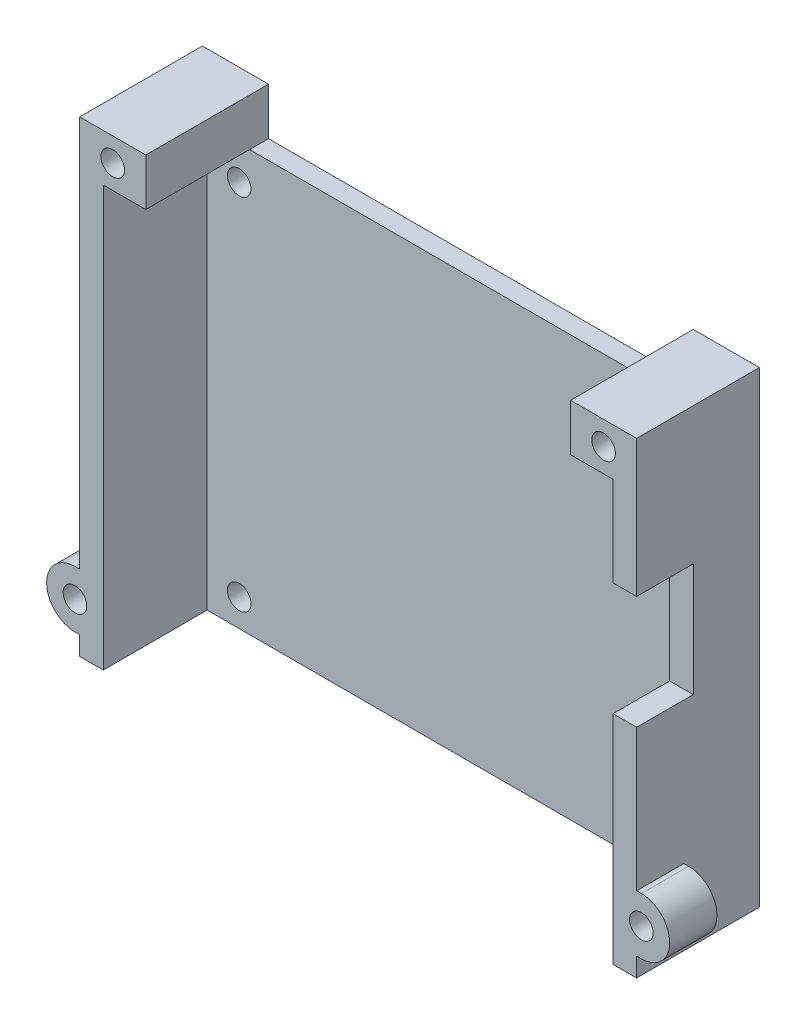
SolidWorks part; units mm, degrees
ref_plane "Front Plane" through (0, 0, 0) normal (0, 0, 1) x (1, 0, 0)
ref_plane "Top Plane" through (0, 0, 0) normal (0, 1, 0) x (1, 0, 0)
ref_plane "Right Plane" through (0, 0, 0) normal (1, 0, 0) x (0, 0, -1)
sketch "Sketch1" plane through (0, 0, 0) normal (0, 1, 0) x (1, 0, 0)
  line L0 (0, 0) -> (2.5, 0)
  line L1 (0, 0) -> (59, 0) construction
  line L2 (0, 0) -> (0, 13)
  line L3 (0, 13) -> (59, 13)
  line L4 (59, 0) -> (59, 13)
  line L5 (2.5, 0) -> (2.5, 11)
  line L6 (2.5, 11) -> (56.5, 11)
  line L7 (56.5, 11) -> (56.5, 0)
  line L8 (56.5, 0) -> (59, 0)
  dimension "D1" = 59
  dimension "D2" = 13
  dimension "D3" = 2.5
  dimension "D4" = 11
  dimension "D5" = 54
extrude "Boss-Extrude1" add sketch "Sketch1" along normal blind 44.5
sketch "Sketch2" plane through (59, 0, 0) normal (1, 0, 0) x (0, 0, -1)
  line L0 (0, 0) -> (0, 23) construction
  line L1 (0, 44.5) -> (0, 0) construction
  line L2 (0, 23) -> (6, 23)
  line L3 (6, 23) -> (6, 35)
  line L4 (6, 35) -> (0, 35)
  line L5 (0, 35) -> (0, 23)
  dimension "D1" = 23
  dimension "D2" = 6
  dimension "D3" = 12
extrude "Cut-Extrude1" cut sketch "Sketch2" against normal blind 10
sketch "Sketch3" plane through (0, 0, -13) normal (0, 0, -1) x (-1, 0, 0)
  line L0 (-59, 0) -> (-59, 8) construction
  line L1 (-59, 44.5) -> (-59, 0) construction
  line L2 (-59, 8) -> (-59, 2)
  line L3 (-59, 5) -> (-59.5, 5) construction
  line L4 (-59, 8) -> (-59.5, 8)
  line L5 (-59, 2) -> (-59.5, 2)
  line L6 (0, 0) -> (0, 8) construction
  line L7 (0, 44.5) -> (0, 0) construction
  line L8 (0, 8) -> (0.5, 8)
  line L9 (0, 8) -> (0, 2)
  line L10 (0, 2) -> (0.5, 2)
  line L11 (0, 5) -> (0.5, 5) construction
  arc A0 (-59.5, 8) -> (-59.5, 2) centre (-59.5, 5) ccw
  circle A1 centre (-59.5, 5) radius 1.25
  arc A2 (0.5, 8) -> (0.5, 2) centre (0.5, 5) cw
  circle A3 centre (0.5, 5) radius 1.25
  line M5 (0, 0) -> (0, 44.5)
  line M7 (-59, 44.5) -> (-59, 0)
  dimension "D4" = 3
  dimension "D5" = 2.5
  dimension "D11" = 3
  dimension "D12" = 2.5
  dimension "D1" = 8
  dimension "D2" = 6
  dimension "D3" = 0.5
  dimension "D6" = 8
  dimension "D7" = 0.5
  dimension "D8" = 6
  dimension "D9" = 0.5
extrude "Boss-Extrude2" add sketch "Sketch3" against normal blind 13 contours A1 L4 A0 L5 M7 | A3 L10 A2 L8 M5 region at (59.0695, 7.0728, -13) region at (-0.25, 7.9305, -13)
extrude "Cut-Extrude2" cut sketch "Sketch3<3>" against normal blind 13 contours L2 A1 | L9 A3 region at (58.6906, 5, -13) region at (0.3094, 5, -13)
sketch "Sketch3<3>" plane through (0, 0, -13) normal (0, 0, -1) x (-1, 0, 0) same geometry as "Sketch3"
sketch "Sketch4" plane through (0, 44.5, 0) normal (0, 1, 0) x (1, 0, 0)
  line L0 (59, 13) -> (0, 13) construction
  line L1 (0, 0) -> (7, 0)
  line L2 (0, 0) -> (0, 13)
  line L3 (0, 13) -> (7, 13)
  line L4 (7, 0) -> (7, 13)
  line L6 (59, 0) -> (52, 0)
  line L7 (59, 0) -> (59, 13)
  line L8 (59, 13) -> (52, 13)
  line L9 (52, 0) -> (52, 13)
  dimension "D1" = 7
  dimension "D2" = 7
extrude "Boss-Extrude3" add sketch "Sketch4" along normal blind 5
sketch "Sketch5" plane through (0, 0, -13) normal (0, 0, -1) x (-1, 0, 0)
  line L0 (-59, 49.5) -> (-52, 44.5) construction
  line L1 (0, 49.5) -> (-7, 44.5) construction
  line L2 (-53, 73.35) -> (-6, 73.35) construction
  line L3 (-6, 73.35) -> (-6, 47) construction
  line L4 (-6, 47) -> (-3.5, 47) construction
  line L5 (-52, 49.5) -> (-52, 44.5) construction
  line L6 (-29.5, 73.35) -> (-29.5, -5.4278) construction
  circle A0 centre (-55.5, 47) radius 1.25
  circle A1 centre (-3.5, 47) radius 1.25
  circle A2 centre (-6, 73.35) radius 1.25
  circle A3 centre (-53, 73.35) radius 1.25
  dimension "D1" = 2.5
  dimension "D3" = 2.5
  dimension "D4" = 3.5
extrude "Cut-Extrude3" cut sketch "Sketch5" against normal through all
sketch "Sketch7" plane through (0, 0, -13) normal (0, 0, -1) x (-1, 0, 0)
  line L0 (-59, 0) -> (-59, 2.9) construction
  line L1 (-59, 2) -> (-59, 0) construction
  line L2 (-59, 2.9) -> (0, 2.9) construction
  line L3 (0, 2) -> (0, 0) construction
  line L4 (-53.1, 2.9) -> (-5.9, 2.9)
  line L5 (-53.1, 2.9) -> (-53.1, 40.95) construction
  line L6 (-53.1, 40.95) -> (-5.9, 40.95) construction
  circle A0 centre (-53.1, 2.9) radius 1.25
  circle A1 centre (-5.9, 2.9) radius 1.25
  circle A2 centre (-53.1, 40.95) radius 1.25
  circle A3 centre (-5.9, 40.95) radius 1.25
  point P11 (-29.5, 2.9)
  dimension "D3" = 2.5
  dimension "D4" = 2.5
  dimension "D6" = 2.5
  dimension "D8" = 2.5
  dimension "D1" = 2.9
  dimension "D2" = 47.2
  dimension "D5" = 38.05
  dimension "D7" = 47.2
extrude "Cut-Extrude4" cut sketch "Sketch7" against normal blind 10 contours A2 | A3 | A1 | A0 region at (5.9, 4.1146, -13) region at (54.3146, 2.9, -13) region at (53.1, 40.95, -13) region at (5.9, 40.95, -13)
extrude "Cut-Extrude6" cut sketch "Sketch3<4>" against normal blind 8 contours A1 L4 A0 L5 M7 | A3 L10 A2 L8 M5 region at (59.0695, 7.0728, -13) region at (-0.25, 7.9305, -13)
sketch "Sketch3<4>" plane through (0, 0, -13) normal (0, 0, -1) x (-1, 0, 0) same geometry as "Sketch3"
extrude "Boss-Extrude4" add sketch "Sketch3<5>" against normal blind 7.5 contours L9 A3 | L2 A1 region at (58.6906, 5, -13) region at (0.3094, 5, -13)
sketch "Sketch3<5>" plane through (0, 0, -13) normal (0, 0, -1) x (-1, 0, 0) same geometry as "Sketch3"
